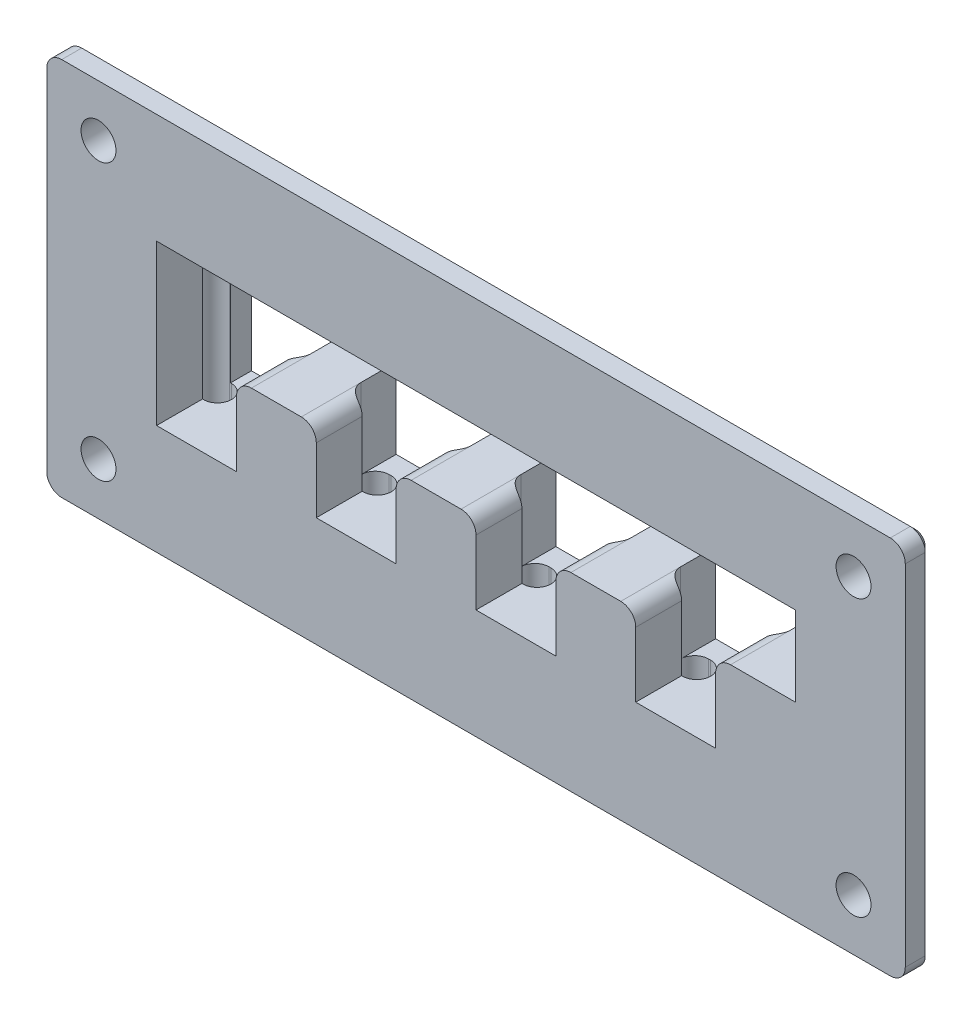
SolidWorks part; units mm, degrees
ref_plane "Front Plane" through (0, 0, 0) normal (0, 0, 1) x (1, 0, 0)
ref_plane "Top Plane" through (0, 0, 0) normal (0, 1, 0) x (1, 0, 0)
ref_plane "Right Plane" through (0, 0, 0) normal (1, 0, 0) x (0, 0, -1)
sketch "Sketch1" plane through (0, 0, 0) normal (0, 0, 1) x (1, 0, 0)
  line L0 (-35, 3) -> (35, 3)
  line L1 (-35, 3) -> (-35, -19)
  line L2 (35, 3) -> (35, -19)
  line L3 (-35, -19) -> (35, -19)
  line L4 (0, 0) -> (0, 3) construction
  line L5 (-32, -8) -> (-35, -8) construction
  line L6 (-32, 0) -> (-32, -16) construction
  line L7 (32, 0) -> (-32, 0) construction
  line L8 (-32, -16) -> (-24, -16) construction
  line L9 (-24, -16) -> (-24, -8) construction
  line L10 (-24, -8) -> (-16, -8) construction
  line L11 (-16, -8) -> (-16, -16) construction
  line L12 (-16, -16) -> (-8, -16) construction
  line L13 (-8, -16) -> (-8, -8) construction
  line L14 (-8, -8) -> (0, -8) construction
  line L15 (0, -8) -> (0, -16) construction
  line L16 (0, -16) -> (8, -16) construction
  line L17 (8, -16) -> (8, -8) construction
  line L18 (8, -8) -> (16, -8) construction
  line L19 (16, -8) -> (16, -16) construction
  line L20 (16, -16) -> (24, -16) construction
  line L21 (24, -16) -> (24, -8) construction
  line L22 (24, -8) -> (32, -8) construction
  line L23 (32, -8) -> (32, 0) construction
  line L24 (-32, 0) -> (-32, -16)
  line L25 (32, 0) -> (-32, 0)
  line L26 (-32, -16) -> (-24, -16)
  line L27 (-24, -16) -> (-24, -8)
  line L28 (-24, -8) -> (-16, -8)
  line L29 (-16, -8) -> (-16, -16)
  line L30 (-16, -16) -> (-8, -16)
  line L31 (-8, -16) -> (-8, -8)
  line L32 (-8, -8) -> (0, -8)
  line L33 (0, -8) -> (0, -16)
  line L34 (0, -16) -> (8, -16)
  line L35 (8, -16) -> (8, -8)
  line L36 (8, -8) -> (16, -8)
  line L37 (16, -8) -> (16, -16)
  line L38 (16, -16) -> (24, -16)
  line L39 (24, -16) -> (24, -8)
  line L40 (24, -8) -> (32, -8)
  line L41 (32, -8) -> (32, 0)
  dimension "D1" = 3
extrude "Boss-Extrude1" add sketch "Sketch1" against normal blind 10
sketch "Sketch2" plane through (0, 0, 0) normal (0, 0, 1) x (1, 0, 0)
  line L0 (0, 3) -> (0, 11) construction
  line L1 (-43, 11) -> (43, 11)
  line L2 (-43, 11) -> (-43, -27)
  line L3 (-43, -27) -> (43, -27)
  line L4 (43, 11) -> (43, -27)
  line L5 (-35, 3) -> (35, 3)
  line L6 (-35, 3) -> (-35, -19)
  line L7 (-35, -19) -> (35, -19)
  line L8 (35, 3) -> (35, -19)
  line L9 (-35, -8) -> (-43, -8) construction
  dimension "D1" = 8
extrude "Boss-Extrude2" add sketch "Sketch2" against normal blind 2.5
sketch "Sketch6" plane through (0, 0, -2.5) normal (0, 0, -1) x (-1, 0, 0)
  line L0 (35, -19) -> (37.818, -21.818) construction
  line L2 (-43, 11) -> (-37.818, 5.818) construction
  line L3 (-37.818, 5.818) -> (-35, 3) construction
  line L4 (37.818, -21.818) -> (-37.818, -21.818) construction
  line L5 (37.818, -21.818) -> (37.818, 5.818) construction
  line L6 (37.818, 5.818) -> (-37.818, 5.818) construction
  line L7 (-37.818, -21.818) -> (-37.818, 5.818) construction
  line L8 (38.7669, -18.2768) -> (35.2256, -19.2256) construction
  line L9 (35.2256, -19.2256) -> (34.2768, -22.7669) construction
  line L10 (34.2768, -22.7669) -> (36.8691, -25.3593) construction
  line L11 (36.8691, -25.3593) -> (40.4104, -24.4104) construction
  line L12 (40.4104, -24.4104) -> (41.3593, -20.8691) construction
  line L13 (41.3593, -20.8691) -> (38.7669, -18.2768) construction
  line L14 (37.818, -21.818) -> (43, -27) construction
  circle A0 centre (37.818, -21.818) radius 1.75
  circle A1 centre (37.818, -21.818) radius 3.175 construction
  circle A2 centre (37.818, -21.818) radius 3.6662 construction
  circle A3 centre (-37.818, 5.818) radius 1.75
  circle A4 centre (37.818, 5.818) radius 1.75
  circle A5 centre (-37.818, -21.818) radius 1.75
  dimension "D1" = 3.5
  dimension "D2" = 6.35
  dimension "D3" = 3.9853
extrude "Cut-Extrude3" cut sketch "Sketch6" against normal up to next
fillet "Fillet1" radius 1.5 15 edges at (24, -8, -5) (16, -8, -5) (8, -8, -5) (0, -8, -5) (-8, -8, -5) (-16, -8, -5) (-24, -8, -5) (-43, -27, -1.25) (-43, 11, -1.25) (-35, -19, -6.25) (-35, 3, -6.25) (35, -19, -6.25) (35, 3, -6.25) (43, -27, -1.25) (43, 11, -1.25)
sketch "Sketch3" plane through (0, 0, 0) normal (0, 1, 0) x (1, 0, 0)
  line L0 (-32.1, 6) -> (-31.9, 6) construction
  line L1 (-32.1, 7.4) -> (-31.9, 7.4)
  line L2 (-32.1, 4.6) -> (-31.9, 4.6)
  circle A0 centre (-32, 6) radius 1.2 construction
  arc A1 (-32, 4.8) -> (-32, 7.2) centre (-32, 6) ccw construction
  circle A2 centre (-32, 6) radius 1.4 construction
  arc A3 (-32.1, 7.4) -> (-32.1, 4.6) centre (-32.1, 6) ccw
  arc A4 (-31.9, 4.6) -> (-31.9, 7.4) centre (-31.9, 6) ccw
  point P8 (-32, 6)
  dimension "D1" = 0.2
  dimension "D2" = 0.2
extrude "Cut-Extrude1" cut sketch "Sketch3" against normal through all both and the other way through all
pattern_linear "LPattern1" count 9 spacing 8 along (1, 0, 0) of "Cut-Extrude1"
sketch "Sketch4" plane through (0, 0, 0) normal (1, 0, 0) x (0, 0, -1)
  line L0 (4.875, -22.9589) -> (5.625, -24.258) construction
  line L1 (10, -19) -> (2.5, -19) construction
  line L2 (10, -17.5) -> (10, -20)
  line L3 (9, -20) -> (10, -20) construction
  line L4 (8.5, -20.866) -> (4.875, -22.9589)
  line L5 (4.5, -23.6084) -> (4.5, -19) construction
  line L6 (5.625, -24.258) -> (8.5, -22.5981)
  line L7 (2.5, -25.5) -> (2.5, 9.5) construction
  line L12 (2.5, -17.5) -> (10, -17.5)
  line L13 (2.5, 1.5) -> (2.5, -17.5)
  line L14 (2.5, -17.5) -> (10, -17.5)
  line L15 (10, -17.5) -> (10, 1.5)
  line L16 (10, 1.5) -> (2.5, 1.5)
  line L17 (10, 1.5) -> (2.5, 1.5)
  arc A0 (8, -19) -> (8.5, -20.866) centre (8, -20) cw
  arc A1 (10, -20) -> (8.5, -22.5981) centre (7, -20) cw
  arc A2 (4.875, -22.9589) -> (5.625, -24.258) centre (5.25, -23.6084) ccw
  dimension "D4" = 1
  dimension "D1" = 1.5
  dimension "D2" = 1
  dimension "D3" = 2
  dimension "D5" = 30
  dimension "D6" = 0
extrude "Boss-Extrude3" [suppressed] add sketch "Sketch4" along normal up to surface and the other way up to surface up to face at (35, -8, -6.25) other way up to face at (-35, -8, -6.25)
sketch "Sketch5" [suppressed] plane through (0, -19, 0) normal (0, -1, 0) x (1, 0, 0)
  line L0 (-35, -3) -> (35, -3) construction
  line L1 (-35, -3) -> (-30.6, -3)
  line L2 (-35, -3) -> (-35, -10)
  line L3 (-35, -10) -> (-30.6, -10)
  line L4 (-30.6, -3) -> (-30.6, -10)
  line L5 (-17.4, -3) -> (-6.6, -3)
  line L6 (-17.4, -3) -> (-17.4, -10)
  line L7 (-17.4, -10) -> (-6.6, -10)
  line L8 (-6.6, -3) -> (-6.6, -10)
  line L9 (35, -10) -> (-35, -10) construction
  line L10 (6.6, -3) -> (17.4, -3)
  line L11 (6.6, -3) -> (6.6, -10)
  line L12 (6.6, -10) -> (17.4, -10)
  line L13 (17.4, -3) -> (17.4, -10)
  line L14 (30.6, -3) -> (35, -3)
  line L15 (30.6, -3) -> (30.6, -10)
  line L16 (30.6, -10) -> (35, -10)
  line L17 (35, -3) -> (35, -10)
  circle A0 centre (-32, -5) radius 1.4 construction
  circle A1 centre (-16, -5) radius 1.4 construction
  circle A2 centre (-8, -5) radius 1.4 construction
  circle A3 centre (8, -5) radius 1.4 construction
  circle A4 centre (16, -5) radius 1.4 construction
  circle A5 centre (32, -5) radius 1.4 construction
  circle A6 centre (-24, -5) radius 2
  circle A7 centre (0, -5) radius 2
  circle A8 centre (24, -5) radius 2
  circle A9 centre (-24, -5) radius 1.4 construction
  circle A10 centre (0, -5) radius 1.4 construction
  circle A11 centre (24, -5) radius 1.4 construction
  dimension "D1" = 4
extrude "Cut-Extrude2" [suppressed] cut sketch "Sketch5" along normal through all
mirror "Mirror1" [suppressed]
ref_plane "Plane1" through (0, 0, -6) normal (0, 0, 1) x (1, 0, 0)
sketch "Sketch7" plane through (0, 0, -6) normal (0, 0, 1) x (1, 0, 0)
  line L1 (-24, -8) -> (-22.5, -8)
  line L2 (-24, -8) -> (-24, -16)
  line L3 (-24, -16) -> (-22.5, -16)
  line L4 (-22.5, -8) -> (-22.5, -16)
  line L5 (-20, -8) -> (-20, -19) construction
  line L9 (-33.5, -19) -> (33.5, -19) construction
  line L10 (-22.5, -8) -> (-17.5, -8) construction
extrude "Cut-Extrude5" cut sketch "Sketch7" against normal up to surface (4 mm away) up to face at (0.0476, -10.253, -10)
ref_plane "Plane2" through (-20, 0, 0) normal (1, 0, 0) x (0, 0, -1)
mirror "Mirror2" about plane through (-20, 0, 0) normal (1, 0, 0) of "Cut-Extrude5"
pattern_linear "LPattern3" count 4 spacing 16 along (1, 0, 0) of "Cut-Extrude5"
pattern_linear "LPattern4" count 3 spacing 16 along (1, 0, 0) of "Mirror2"
chamfer "Chamfer1" distance 0.5 angle 45 34 edges at (34.5607, -18.5607, -10) (35, -8, -10) (34.5607, 2.5607, -10) (0, 3, -10) (-34.5607, 2.5607, -10) (-35, -8, -10) (-34.5607, -18.5607, -10) (0, -19, -10) (20, -16, -10) (12, -8, -10) (4, -16, -10) (-4, -8, -10) (-12, -16, -10) (-20, -8, -10) (-27.25, -16, -10) (-32, -8, -10) (0, 0, -10) (32, -4, -10) (28.75, -8, -10) (-42.5607, 10.5607, -2.5) (-43, -8, -2.5) (-42.5607, -26.5607, -2.5) (0, -27, -2.5) (42.5607, -26.5607, -2.5) (0, 11, -2.5) (42.5607, 10.5607, -2.5) (43, -8, -2.5) (-22.5, -12, -10) (9.5, -12, -10) (-1.5, -12, -10) (-6.5, -12, -10) (-17.5, -12, -10) (25.5, -12, -10) (14.5, -12, -10)
